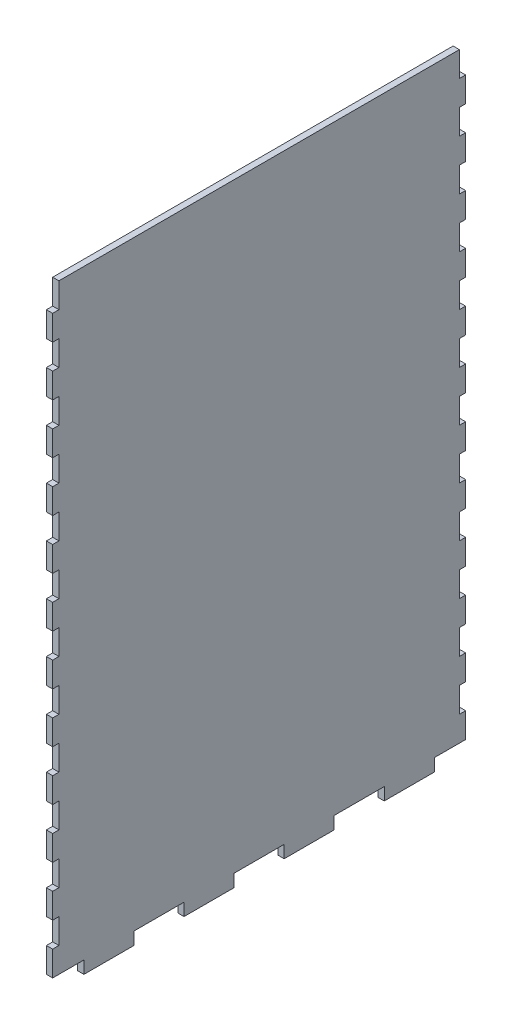
SolidWorks part; units mm, degrees
ref_plane "Front Plane" through (0, 0, 0) normal (0, 0, 1) x (1, 0, 0)
ref_plane "Top Plane" through (0, 0, 0) normal (0, 1, 0) x (1, 0, 0)
ref_plane "Right Plane" through (0, 0, 0) normal (1, 0, 0) x (0, 0, -1)
sketch "Sketch1" plane through (0, 0, 0) normal (1, 0, 0) x (0, 0, -1)
  line L0 (0, 0) -> (203.2, 0)
  line L1 (203.2, 0) -> (203.2, 304.8)
  line L2 (203.2, 304.8) -> (0, 304.8)
  line L3 (0, 304.8) -> (0, 0)
  line L4 (101.6, 304.8) -> (101.6, 0) construction
  line L5 (0, 0) -> (-3.175, 0)
  line L6 (-3.175, 0) -> (-3.175, 12.7)
  line L7 (-3.175, 12.7) -> (0, 12.7)
  line L8 (0, 12.7) -> (0, 0)
  line L9 (0, 25.4) -> (-3.175, 25.4)
  line L10 (-3.175, 25.4) -> (-3.175, 38.1)
  line L11 (-3.175, 38.1) -> (0, 38.1)
  line L12 (0, 38.1) -> (0, 25.4)
  line L13 (0, 50.8) -> (-3.175, 50.8)
  line L14 (-3.175, 50.8) -> (-3.175, 63.5)
  line L15 (-3.175, 63.5) -> (0, 63.5)
  line L16 (0, 63.5) -> (0, 50.8)
  line L17 (0, 76.2) -> (-3.175, 76.2)
  line L18 (-3.175, 76.2) -> (-3.175, 88.9)
  line L19 (-3.175, 88.9) -> (0, 88.9)
  line L20 (0, 88.9) -> (0, 76.2)
  line L21 (0, 101.6) -> (-3.175, 101.6)
  line L22 (-3.175, 101.6) -> (-3.175, 114.3)
  line L23 (-3.175, 114.3) -> (0, 114.3)
  line L24 (0, 114.3) -> (0, 101.6)
  line L25 (0, 127) -> (-3.175, 127)
  line L26 (-3.175, 127) -> (-3.175, 139.7)
  line L27 (-3.175, 139.7) -> (0, 139.7)
  line L28 (0, 139.7) -> (0, 127)
  line L29 (0, 152.4) -> (-3.175, 152.4)
  line L30 (-3.175, 152.4) -> (-3.175, 165.1)
  line L31 (-3.175, 165.1) -> (0, 165.1)
  line L32 (0, 165.1) -> (0, 152.4)
  line L33 (0, 177.8) -> (-3.175, 177.8)
  line L34 (-3.175, 177.8) -> (-3.175, 190.5)
  line L35 (-3.175, 190.5) -> (0, 190.5)
  line L36 (0, 190.5) -> (0, 177.8)
  line L37 (0, 203.2) -> (-3.175, 203.2)
  line L38 (-3.175, 203.2) -> (-3.175, 215.9)
  line L39 (-3.175, 215.9) -> (0, 215.9)
  line L40 (0, 215.9) -> (0, 203.2)
  line L41 (0, 228.6) -> (-3.175, 228.6)
  line L42 (-3.175, 228.6) -> (-3.175, 241.3)
  line L43 (-3.175, 241.3) -> (0, 241.3)
  line L44 (0, 241.3) -> (0, 228.6)
  line L45 (0, 254) -> (-3.175, 254)
  line L46 (-3.175, 254) -> (-3.175, 266.7)
  line L47 (-3.175, 266.7) -> (0, 266.7)
  line L48 (0, 266.7) -> (0, 254)
  line L49 (0, 279.4) -> (-3.175, 279.4)
  line L50 (-3.175, 279.4) -> (-3.175, 292.1)
  line L51 (-3.175, 292.1) -> (0, 292.1)
  line L52 (0, 292.1) -> (0, 279.4)
  line L53 (0, 0) -> (0, 25.4) construction
  line L54 (12.7, 0) -> (12.7, -6.35)
  line L55 (12.7, -6.35) -> (38.1, -6.35)
  line L56 (38.1, -6.35) -> (38.1, 0)
  line L57 (38.1, 0) -> (12.7, 0)
  line L58 (88.9, 0) -> (63.5, 0)
  line L59 (63.5, 0) -> (63.5, -6.35)
  line L60 (63.5, -6.35) -> (88.9, -6.35)
  line L61 (88.9, -6.35) -> (88.9, 0)
  line L62 (139.7, 0) -> (114.3, 0)
  line L63 (114.3, 0) -> (114.3, -6.35)
  line L64 (114.3, -6.35) -> (139.7, -6.35)
  line L65 (139.7, -6.35) -> (139.7, 0)
  line L66 (190.5, 0) -> (165.1, 0)
  line L67 (165.1, 0) -> (165.1, -6.35)
  line L68 (165.1, -6.35) -> (190.5, -6.35)
  line L69 (190.5, -6.35) -> (190.5, 0)
  line L70 (38.1, 0) -> (88.9, 0) construction
  line L71 (203.2, 12.7) -> (203.2, 0)
  line L72 (206.375, 12.7) -> (203.2, 12.7)
  line L73 (206.375, 0) -> (206.375, 12.7)
  line L74 (203.2, 0) -> (206.375, 0)
  line L75 (203.2, 38.1) -> (203.2, 25.4)
  line L76 (206.375, 38.1) -> (203.2, 38.1)
  line L77 (206.375, 25.4) -> (206.375, 38.1)
  line L78 (203.2, 25.4) -> (206.375, 25.4)
  line L79 (203.2, 63.5) -> (203.2, 50.8)
  line L80 (206.375, 63.5) -> (203.2, 63.5)
  line L81 (206.375, 50.8) -> (206.375, 63.5)
  line L82 (203.2, 50.8) -> (206.375, 50.8)
  line L83 (203.2, 88.9) -> (203.2, 76.2)
  line L84 (206.375, 88.9) -> (203.2, 88.9)
  line L85 (206.375, 76.2) -> (206.375, 88.9)
  line L86 (203.2, 76.2) -> (206.375, 76.2)
  line L87 (203.2, 114.3) -> (203.2, 101.6)
  line L88 (206.375, 114.3) -> (203.2, 114.3)
  line L89 (206.375, 101.6) -> (206.375, 114.3)
  line L90 (203.2, 101.6) -> (206.375, 101.6)
  line L91 (203.2, 139.7) -> (203.2, 127)
  line L92 (206.375, 139.7) -> (203.2, 139.7)
  line L93 (206.375, 127) -> (206.375, 139.7)
  line L94 (203.2, 127) -> (206.375, 127)
  line L95 (203.2, 165.1) -> (203.2, 152.4)
  line L96 (206.375, 165.1) -> (203.2, 165.1)
  line L97 (206.375, 152.4) -> (206.375, 165.1)
  line L98 (203.2, 152.4) -> (206.375, 152.4)
  line L99 (203.2, 190.5) -> (203.2, 177.8)
  line L100 (206.375, 190.5) -> (203.2, 190.5)
  line L101 (206.375, 177.8) -> (206.375, 190.5)
  line L102 (203.2, 177.8) -> (206.375, 177.8)
  line L103 (203.2, 215.9) -> (203.2, 203.2)
  line L104 (206.375, 215.9) -> (203.2, 215.9)
  line L105 (206.375, 203.2) -> (206.375, 215.9)
  line L106 (203.2, 203.2) -> (206.375, 203.2)
  line L107 (203.2, 241.3) -> (203.2, 228.6)
  line L108 (206.375, 241.3) -> (203.2, 241.3)
  line L109 (206.375, 228.6) -> (206.375, 241.3)
  line L110 (203.2, 228.6) -> (206.375, 228.6)
  line L111 (203.2, 266.7) -> (203.2, 254)
  line L112 (206.375, 266.7) -> (203.2, 266.7)
  line L113 (206.375, 254) -> (206.375, 266.7)
  line L114 (203.2, 254) -> (206.375, 254)
  line L115 (203.2, 292.1) -> (203.2, 279.4)
  line L116 (206.375, 292.1) -> (203.2, 292.1)
  line L117 (206.375, 279.4) -> (206.375, 292.1)
  line L118 (203.2, 279.4) -> (206.375, 279.4)
  dimension "D1" = 203.2
  dimension "D2" = 304.8
  dimension "D3" = 3.175
  dimension "D4" = 12.7
  dimension "D6" = 25.4
  dimension "D7" = 6.35
  dimension "D8" = 25.4
  dimension "D9" = 12.7
  dimension "D11" = 50.8
  dimension "D5" = 12
  dimension "D10" = 4
extrude "Boss-Extrude1" add sketch "Sketch1" along normal blind 3.175 contours L51 L50 L49 L3 | L47 L46 L45 L3 | L43 L42 L41 L3 | L39 L38 L37 L3 | L35 L34 L33 L3 | L31 L30 L29 L3 | L27 L26 L25 L3 | L23 L22 L21 L3 | L19 L18 L17 L3 | L15 L14 L13 L3 | L11 L10 L9 L3 | L2 L3 L0 L1 | L7 L6 L5 L3 | L55 L56 L0 L54 | L60 L61 L0 L59 | L64 L65 L0 L63 | L68 L69 L0 L67 | L1 L74 L73 L72 | L1 L78 L77 L76 | L1 L82 L81 L80 | L1 L86 L85 L84 | L1 L90 L89 L88 | L1 L94 L93 L92 | L1 L98 L97 L96 | L1 L102 L101 L100 | L1 L106 L105 L104 | L1 L110 L109 L108 | L1 L114 L113 L112 | L1 L118 L117 L116 region at (0, 152.4, -101.6) region at (0, 6.35, 1.5875) region at (0, -3.175, -25.4) region at (0, 31.75, 1.5875) region at (0, -3.175, -76.2) region at (0, 57.15, 1.5875) region at (0, -3.175, -127) region at (0, 82.55, 1.5875) region at (0, -3.175, -177.8) region at (0, 107.95, 1.5875) region at (0, 6.35, -204.7875) region at (0, 133.35, 1.5875) region at (0, 31.75, -204.7875) region at (0, 158.75, 1.5875) region at (0, 57.15, -204.7875) region at (0, 184.15, 1.5875) region at (0, 82.55, -204.7875) region at (0, 209.55, 1.5875) region at (0, 107.95, -204.7875) region at (0, 234.95, 1.5875) region at (0, 133.35, -204.7875) region at (0, 260.35, 1.5875) region at (0, 158.75, -204.7875) region at (0, 285.75, 1.5875) region at (0, 184.15, -204.7875) region at (0, 209.55, -204.7875) region at (0, 285.75, -204.7875) region at (0, 234.95, -204.7875) region at (0, 260.35, -204.7875)
equation "\"wall_thickness\" = 0.125in"
equation "\"base_thickness\" = 0.25in"
equation "\"D3@Sketch1\"=\"wall_thickness\""
equation "\"D7@Sketch1\"=\"base_thickness\""
equation "\"D1@Boss-Extrude1\"=\"wall_thickness\""
